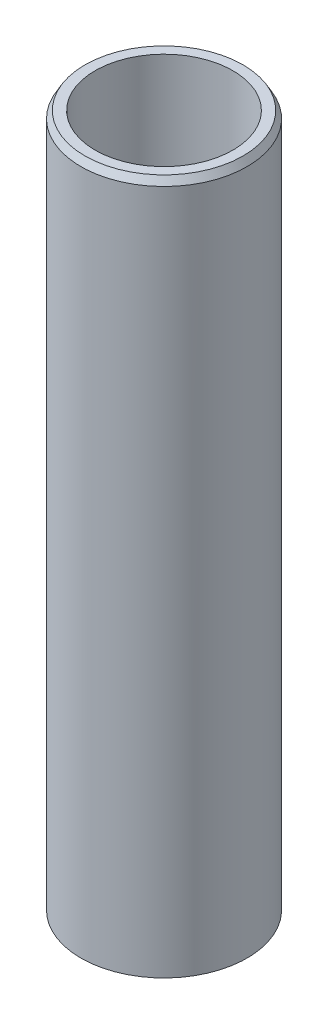
SolidWorks part; units mm, degrees
ref_plane "Front Plane" through (0, 0, 0) normal (0, 0, 1) x (1, 0, 0)
ref_plane "Top Plane" through (0, 0, 0) normal (0, 1, 0) x (1, 0, 0)
ref_plane "Right Plane" through (0, 0, 0) normal (1, 0, 0) x (0, 0, -1)
sketch "Sketch1" plane through (0, 0, 0) normal (0, 1, 0) x (1, 0, 0)
  circle A0 centre (0, 0) radius 55
  dimension "SHAFT_OD" = 110
extrude "Boss-Extrude1" add sketch "Sketch1" along normal blind 460.9406
sketch "Sketch2" plane through (0, 0, 0) normal (0, 1, 0) x (1, 0, 0)
  circle A0 centre (0, 0) radius 45.5774
  dimension "BORE_D" = 91.1547
extrude "Cut-Extrude1" cut sketch "Sketch2" along normal through all
chamfer "Chamfer1" distance 4.7188 angle 30 2 edges at (0, 460.9406, 55) (0, 0, 55) first distance on face at (0, 460.9406, 55) first distance on face at (0, 0, 45.5774)
